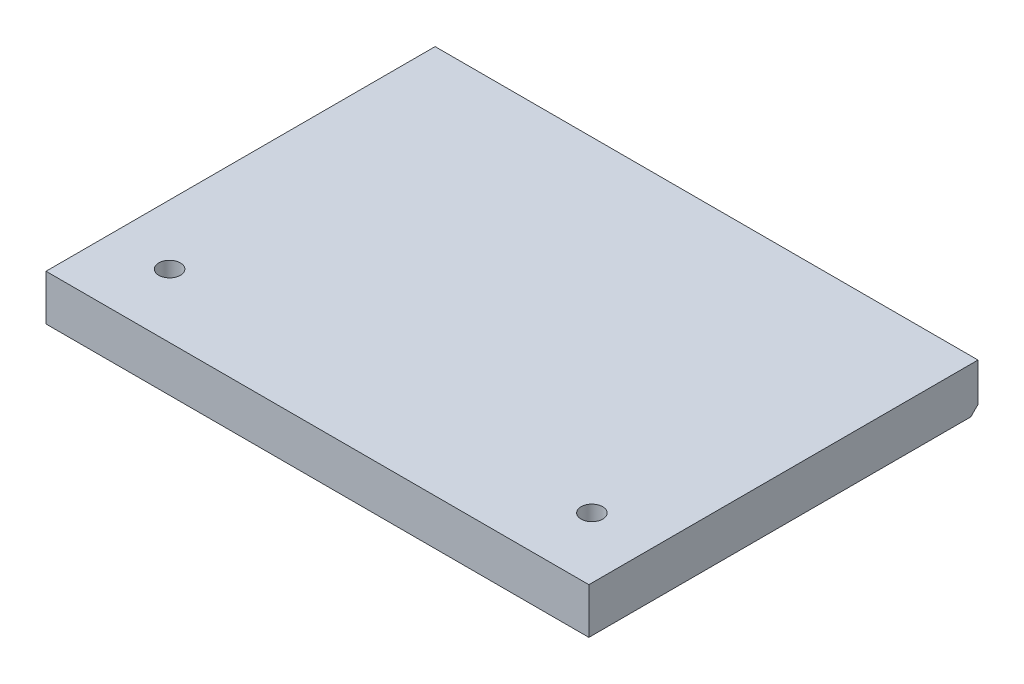
SolidWorks part; units mm, degrees
ref_plane "Front Plane" through (0, 0, 0) normal (0, 0, 1) x (1, 0, 0)
ref_plane "Top Plane" through (0, 0, 0) normal (0, 1, 0) x (1, 0, 0)
ref_plane "Right Plane" through (0, 0, 0) normal (1, 0, 0) x (0, 0, -1)
sketch "Sketch1" plane through (0, 0, 0) normal (0, 1, 0) x (1, 0, 0)
  line L1 (-86.2, 96.2) -> (86.2, 96.2)
  line L2 (-86.2, 96.2) -> (-86.2, -96.2)
  line L3 (-86.2, -96.2) -> (86.2, -96.2)
  line L4 (86.2, 96.2) -> (86.2, -96.2)
  line L5 (-86.2, 96.2) -> (86.2, -96.2) construction
  line L6 (-86.2, -96.2) -> (86.2, 96.2) construction
  point P0 (0, 0)
  dimension "D1" = 192.4
  dimension "D2" = 172.4
extrude "Boss-Extrude1" add sketch "Sketch1" along normal blind 6.35
sketch "Sketch2" plane through (0, 6.35, 0) normal (0, 1, 0) x (1, 0, 0)
  line L1 (-86.2, 96.2) -> (-45.2, 96.2)
  line L2 (-86.2, 96.2) -> (-86.2, 55.2)
  line L3 (-86.2, 55.2) -> (-45.2, 55.2)
  line L4 (-45.2, 96.2) -> (-45.2, 55.2)
  dimension "D1" = 41
extrude "Cut-Extrude1" cut sketch "Sketch2" against normal up to next
sketch "Sketch3" plane through (0, 6.35, 0) normal (0, 1, 0) x (1, 0, 0)
  line L0 (-66.2, 55.2) -> (-66.2, -96.2) construction
  line L1 (-86.2, 55.2) -> (-45.2, 55.2) construction
  line L2 (-86.2, -96.2) -> (86.2, -96.2) construction
  line L3 (-45.2, 76.2) -> (86.2, 76.2) construction
  line L4 (-45.2, 55.2) -> (-45.2, 96.2) construction
  line L5 (86.2, -96.2) -> (86.2, 96.2) construction
  line L6 (86.2, 96.2) -> (-45.2, 96.2) construction
  line L7 (-86.2, 55.2) -> (-86.2, -96.2) construction
  point P16 (-66.2, 34.3955)
  point P18 (-66.2, -56.2)
  point P20 (-26.2, 76.2)
  point P22 (66.2, 76.2)
  dimension "D1" = 20
  dimension "D2" = 20
  dimension "D3" = 20
  dimension "D4" = 19
  dimension "D5" = 20.8045
  dimension "D6" = 40
hole_wizard "CBORE for M4 SHCS1" positions "Sketch3" profile "Sketch4" counterbore size "M4" standard "ANSI Metric" end condition up to next
sketch "Sketch4" plane through (66.2, 6.35, -76.2) normal (1, 0, 0) x (0, 0, 1)
  line L0 (0, 0) -> (0, 6.35)
  line L1 (0, 6.35) -> (2.25, 6.35)
  line L3 (2.25, 6.35) -> (2.25, 4)
  line L4 (2.25, 4) -> (4, 4)
  line L5 (4, 4) -> (4, 0)
  line L7 (4, 0) -> (0, 0)
  line L11 (0, -6.35) -> (0, 107.95) construction
  dimension "Thru Hole Dia." = 4.5
  dimension "Thru Hole Depth" = 6.35
  dimension "C'Bore Dia." = 8
  dimension "C'Bore Depth" = 4
sketch "Sketch5" plane through (0, 6.35, 0) normal (0, 1, 0) x (1, 0, 0)
  line L0 (-86.2, -96.2) -> (86.2, -96.2) construction
  line L1 (-76.36, -105.09) -> (-56.04, -105.09) construction
  line L2 (-76.36, -105.09) -> (-76.36, -87.31) construction
  line L3 (-76.36, -87.31) -> (-56.04, -87.31) construction
  line L4 (-56.04, -105.09) -> (-56.04, -87.31) construction
  line L5 (-76.36, -105.09) -> (-56.04, -87.31) construction
  line L6 (-76.36, -87.31) -> (-56.04, -105.09) construction
  line L7 (-86.2, 55.2) -> (-86.2, -96.2) construction
  circle A0 centre (-76.36, -87.31) radius 1.2
  circle A1 centre (-56.04, -87.31) radius 1.2
  point P0 (-66.2, -96.2)
  dimension "D4" = 2.4
  dimension "D1" = 20
  dimension "D2" = 20.32
  dimension "D3" = 17.78
extrude "Cut-Extrude3" cut sketch "Sketch5" against normal up to next
sketch "Sketch6" plane through (0, 6.35, 0) normal (0, 1, 0) x (1, 0, 0)
  circle A0 centre (-76.36, -87.31) radius 1.4
  circle A1 centre (-56.04, -87.31) radius 1.4
  dimension "D1" = 2.8
extrude "Cut-Extrude4" cut sketch "Sketch6" against normal blind 4
sketch "Sketch7" plane through (0, 6.35, 0) normal (0, 1, 0) x (1, 0, 0)
  line L0 (-86.2, -96.2) -> (86.2, -96.2) construction
  line L5 (-86.2, -96.2) -> (86.2, -96.2) construction
  line L6 (-40, -146.2) -> (40, -146.2) construction
  line L7 (-40, -146.2) -> (-40, -46.2) construction
  line L8 (-35.24, -141.44) -> (23.46, -141.44) construction
  line L9 (-35.24, -141.44) -> (-35.24, -50.96) construction
  line L10 (-35.24, -50.96) -> (23.46, -50.96) construction
  line L11 (23.46, -141.44) -> (23.46, -50.96) construction
  line L12 (-35.24, -141.44) -> (23.46, -50.96) construction
  line L13 (-35.24, -50.96) -> (23.46, -141.44) construction
  line L14 (-40, -46.2) -> (40, -46.2) construction
  line L15 (40, -146.2) -> (40, -46.2) construction
  line L16 (-40, -146.2) -> (40, -46.2) construction
  line L17 (-40, -46.2) -> (40, -146.2) construction
  line L18 (86.2, -96.2) -> (86.2, 96.2) construction
  circle A0 centre (-35.24, -50.96) radius 1.35
  circle A1 centre (23.46, -50.96) radius 1.35
  point P0 (-5.89, -96.2)
  point P2 (0, -96.2)
  point P7 (-5.89, -96.2)
  dimension "D7" = 2.7
  dimension "D3" = 90.48
  dimension "D4" = 58.7
  dimension "D1" = 80
  dimension "D2" = 100
  dimension "D5" = 4.76
  dimension "D6" = 4.76
extrude "Cut-Extrude5" cut sketch "Sketch7" against normal up to next
sketch "Sketch8" plane through (0, 6.35, 0) normal (0, 1, 0) x (1, 0, 0)
  circle A0 centre (-35.24, -50.96) radius 1.5
  circle A1 centre (23.46, -50.96) radius 1.5
  dimension "D1" = 3
extrude "Cut-Extrude6" cut sketch "Sketch8" against normal blind 5 contours A0 | A1
sketch "Sketch9" plane through (0, 6.35, 0) normal (0, 1, 0) x (1, 0, 0)
  line L0 (78.7, -96.2) -> (78.7, 96.2)
  line L1 (-86.2, -96.2) -> (86.2, -96.2) construction
  line L2 (86.2, -96.2) -> (86.2, 96.2) construction
  line L3 (86.2, 96.2) -> (-45.2, 96.2) construction
  dimension "D1" = 7.5
extrude "Extrude-Thin1" add sketch "Sketch9" along normal blind 3 thin thin type mid plane wall 3
chamfer "Chamfer1" distance 3 angle 45 2 edges at (77.2, 6.35, 0) (80.2, 6.35, 0)
chamfer "Chamfer2" distance 1 angle 45 2 edges at (86.2, 0, 0) (0, 0, 96.2)
mirror "Mirror1"
delete or keep bodies "Body-Delete/Keep 1" type delete bodies bodies 109
sketch "Sketch11" plane through (0, 6.35, 0) normal (0, 1, 0) x (1, 0, 0)
  line L1 (-132.1779, -55.3537) -> (153.1121, -55.3537)
  line L2 (-132.1779, -55.3537) -> (-132.1779, -314.3542)
  line L3 (-132.1779, -314.3542) -> (153.1121, -314.3542)
  line L4 (153.1121, -55.3537) -> (153.1121, -314.3542)
  line L5 (-43.5724, -84.5643) -> (31.8882, -84.5643)
  line L6 (-43.5724, -84.5643) -> (-43.5724, -150.2881)
  line L7 (-43.5724, -150.2881) -> (31.8882, -150.2881)
  line L8 (31.8882, -84.5643) -> (31.8882, -150.2881)
extrude "Cut-Extrude8" cut sketch "Sketch11" against normal through all both and the other way through all
equation "\"D1@Sketch1\"=384.8/2"
equation "\"D6@Sketch7\"=\"D5@Sketch7\""
